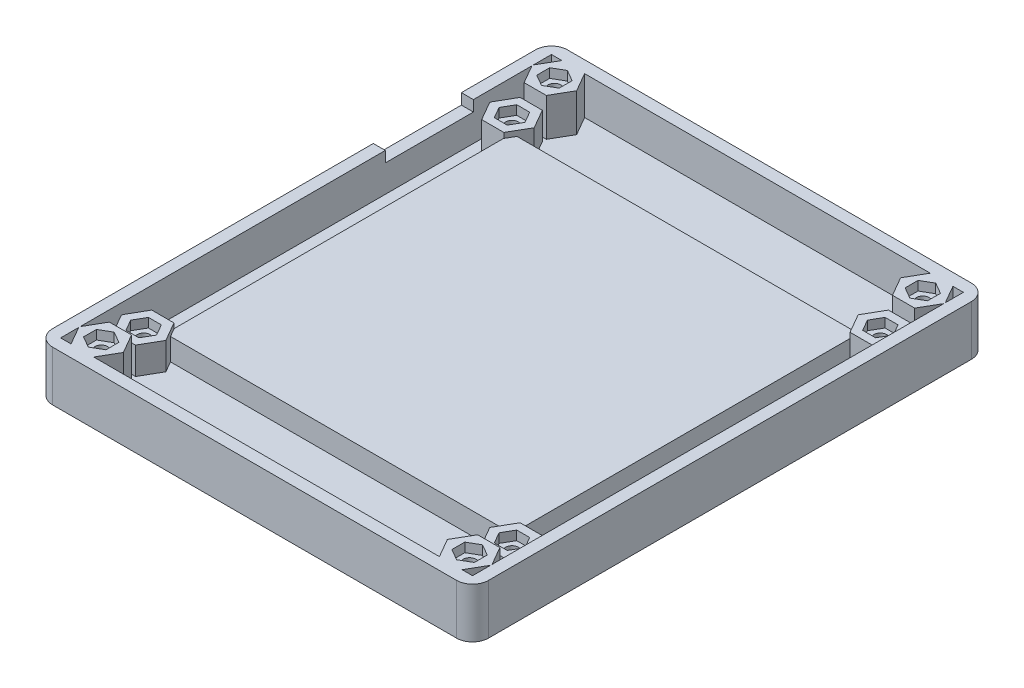
SolidWorks part; units mm, degrees
ref_plane "Přední rovina" through (0, 0, 0) normal (0, 0, 1) x (1, 0, 0)
ref_plane "Horní rovina" through (0, 0, 0) normal (0, 1, 0) x (1, 0, 0)
ref_plane "Pravá rovina" through (0, 0, 0) normal (1, 0, 0) x (0, 0, -1)
sketch "Skica1" plane through (0, 0, 0) normal (0, 1, 0) x (1, 0, 0)
  line L0 (0, 0) -> (-100, 100) construction
  line L1 (-50, 50) -> (50, 50) construction
  line L2 (-50, 50) -> (-50, -50) construction
  line L3 (-50, -50) -> (50, -50) construction
  line L4 (50, 50) -> (50, -50) construction
  line L5 (-50, 50) -> (50, -50) construction
  line L6 (-50, -50) -> (50, 50) construction
  line L7 (-47.6166, 43.2) -> (-44.3834, 43.2)
  line L8 (-44.3834, 43.2) -> (-42.7668, 46)
  line L9 (-42.7668, 46) -> (-44.3834, 48.8)
  line L10 (-44.3834, 48.8) -> (-47.6166, 48.8)
  line L11 (-47.6166, 48.8) -> (-49.2332, 46)
  line L12 (-49.2332, 46) -> (-47.6166, 43.2)
  line L13 (-48.7713, 41.2) -> (-43.2287, 41.2)
  line L14 (-43.2287, 41.2) -> (-40.4574, 46)
  line L15 (-40.4574, 46) -> (-43.2287, 50.8)
  line L16 (-43.2287, 50.8) -> (-48.7713, 50.8)
  line L17 (-48.7713, 50.8) -> (-51.5426, 46)
  line L18 (-51.5426, 46) -> (-48.7713, 41.2)
  line L19 (0, 81.3987) -> (0, -91.9033) construction
  line L20 (-46, 53.3668) -> (-43.2, 54.9834)
  line L21 (-43.2, 54.9834) -> (-43.2, 58.2166)
  line L22 (-43.2, 58.2166) -> (-46, 59.8332)
  line L23 (-46, 59.8332) -> (-48.8, 58.2166)
  line L24 (-48.8, 58.2166) -> (-48.8, 54.9834)
  line L25 (-48.8, 54.9834) -> (-46, 53.3668)
  line L26 (-48.7713, 51.8) -> (-43.2287, 51.8)
  line L27 (-43.2287, 51.8) -> (-40.4574, 56.6)
  line L28 (-40.4574, 56.6) -> (-43.2287, 61.4)
  line L29 (-43.2287, 61.4) -> (-48.7713, 61.4)
  line L30 (-48.7713, 61.4) -> (-51.5426, 56.6)
  line L31 (-51.5426, 56.6) -> (-48.7713, 51.8)
  line L36 (74.9355, -74.9355) -> (-74.9355, 74.9355) construction
  line L37 (74.9355, 74.9355) -> (-74.9355, -74.9355) construction
  line L38 (-54.4426, -64.3) -> (54.4426, -64.3)
  line L39 (-54.4426, -64.3) -> (-54.4426, 64.3)
  line L40 (-54.4426, 64.3) -> (54.4426, 64.3)
  line L41 (54.4426, -64.3) -> (54.4426, 64.3)
  line L42 (-54.4426, -64.3) -> (54.4426, 64.3) construction
  line L43 (-54.4426, 64.3) -> (54.4426, -64.3) construction
  line L44 (-106.951, 0) -> (125.2961, 0) construction
  line L45 (-46, 37.8836) -> (-46, 68.4593) construction
  line L47 (-51.4426, -61.3) -> (51.4426, -61.3)
  line L48 (-51.4426, -61.3) -> (-51.4426, 61.3)
  line L49 (-51.4426, 61.3) -> (51.4426, 61.3)
  line L50 (51.4426, -61.3) -> (51.4426, 61.3)
  line L51 (-51.4426, -61.3) -> (51.4426, 61.3) construction
  line L52 (-51.4426, 61.3) -> (51.4426, -61.3) construction
  circle A0 centre (-46, 46) radius 2.8 construction
  circle A1 centre (-46, 46) radius 4.8 construction
  circle A2 centre (-46, 56.6) radius 2.8 construction
  circle A3 centre (-46, 56.6) radius 4.8 construction
  circle A4 centre (-46, 46) radius 1.6
  circle A5 centre (-46, 56.6) radius 1.6
  point P0 (0, 0)
  point P7 (-41.8431, 43.6)
  dimension "D9" = 3
  dimension "D10" = 3
  dimension "D11" = 0.1
  dimension "D12" = 0.1
  dimension "D13" = 3.2
  dimension "D14" = 3.2
  dimension "D1" = 100
  dimension "D2" = 100
  dimension "D3" = 5.6
  dimension "D4" = 4
  dimension "D5" = 9.6
  dimension "D6" = 5.6
  dimension "D7" = 9.6
  dimension "D8" = 1
extrude "Přidat vysunutím25" add sketch "Skica1" against normal blind 3 contours L49 L48 L30 | L20 L21 L22 L23 L24 L25 | L7 L8 L9 L10 L11 L12 | L48 L47 L50 L49 | L13 L14 L15 L16 L17 L18 | L26 L27 L28 L29 L30 L31 region at (-50.5714, 0, -59.7911)
extrude "Přidat vysunutím26" add sketch "Skica1<21>" against normal blind 3 and the other way blind 9.5 contours L38 L41 L40 L39 L50 L47 L48 L18 L17 L31 L30 L49 L29 L28 | L18 L48 L17 | L31 L48 L30 | L30 L49 L28 L29 region at (-51.4759, 0, -46) region at (-51.4759, 0, -56.6) region at (-46, 0, -61.3498) region at (-52.7575, 0, 0)
sketch "Skica1<21>" plane through (0, 0, 0) normal (0, 1, 0) x (1, 0, 0) same geometry as "Skica1"
extrude "Přidat vysunutím28" add sketch "Skica1<23>" along normal blind 6.8 contours L48 L18 L13 L14 L15 L16 L17 L12 L11 L10 L9 L8 L7 | L18 L48 L17 region at (-49.9806, 0, -43.5863) region at (-51.4759, 0, -46)
sketch "Skica1<23>" plane through (0, 0, 0) normal (0, 1, 0) x (1, 0, 0) same geometry as "Skica1"
extrude "Přidat vysunutím29" add sketch "Skica1<24>" along normal blind 4.5 contours L11 L12 L7 L8 L9 L10 region at (-48.3508, 0, -44.6428)
sketch "Skica1<24>" plane through (0, 0, 0) normal (0, 1, 0) x (1, 0, 0) same geometry as "Skica1"
pattern_linear "LinPole3" count 2 spacing 92 along (1, 0, 0) count 2 spacing 92 along (0, 0, 1) of "Přidat vysunutím28", "Přidat vysunutím29"
extrude "Přidat vysunutím30" add sketch "Skica1<25>" along normal blind 9.5 contours L49 L30 L48 L31 L26 L27 L28 L25 L24 L23 L22 L21 L20 | L30 L49 L28 L29 | L31 L48 L30 region at (-51.2973, 0, -56.6) region at (-51.4759, 0, -56.6) region at (-46, 0, -61.3498)
sketch "Skica1<25>" plane through (0, 0, 0) normal (0, 1, 0) x (1, 0, 0) same geometry as "Skica1"
extrude "Přidat vysunutím31" add sketch "Skica1<26>" along normal blind 7.2 contours L24 L25 L20 L21 L22 L23 A5 region at (-47.3572, 0, -54.2492)
sketch "Skica1<26>" plane through (0, 0, 0) normal (0, 1, 0) x (1, 0, 0) same geometry as "Skica1"
pattern_linear "LinPole4" count 2 spacing 92 along (1, 0, 0) count 2 spacing 113.2 along (0, 0, 1) of "Přidat vysunutím31", "Přidat vysunutím30"
sketch "Skica8" plane through (0, 0, 0) normal (0, 1, 0) x (1, 0, 0)
  line L1 (-43.2691, -43.2691) -> (43.2691, -43.2691)
  line L2 (-43.2691, -43.2691) -> (-43.2691, 43.2691)
  line L3 (-43.2691, 43.2691) -> (43.2691, 43.2691)
  line L4 (43.2691, -43.2691) -> (43.2691, 43.2691)
  line L5 (-43.2691, -43.2691) -> (43.2691, 43.2691) construction
  line L6 (-43.2691, 43.2691) -> (43.2691, -43.2691) construction
  point P0 (0, 0)
  dimension "D1" = 86.5383
extrude "Přidat vysunutím32" add sketch "Skica8" along normal blind 5.5
fillet "Zaoblit4" radius 4 4 edges at (-54.4426, 3.25, 64.3) (54.4426, 3.25, 64.3) (54.4426, 3.25, -64.3) (-54.4426, 3.25, -64.3)
sketch "Skica9" plane through (-54.4426, 0, 0) normal (-1, 0, 0) x (0, 0, 1)
  line L0 (60.3, 9.5) -> (-60.3, 9.5) construction
  line L1 (-19.8, 6.8) -> (-41.8, 6.8)
  line L2 (-19.8, 6.8) -> (-19.8, 9.5)
  line L3 (-19.8, 9.5) -> (-41.8, 9.5)
  line L4 (-41.8, 6.8) -> (-41.8, 9.5)
  line L5 (-19.8, 6.8) -> (-41.8, 9.5) construction
  line L6 (-19.8, 9.5) -> (-41.8, 6.8) construction
  line L7 (-64.3, -3) -> (-64.3, 9.5) construction
  point P0 (-30.8, 8.15)
  dimension "D1" = 22
  dimension "D2" = 22.5
  dimension "D3" = 2.7
extrude "Odebrat vysunutím1" cut sketch "Skica9" against normal blind 10 contours L4 L3 L2 L1
